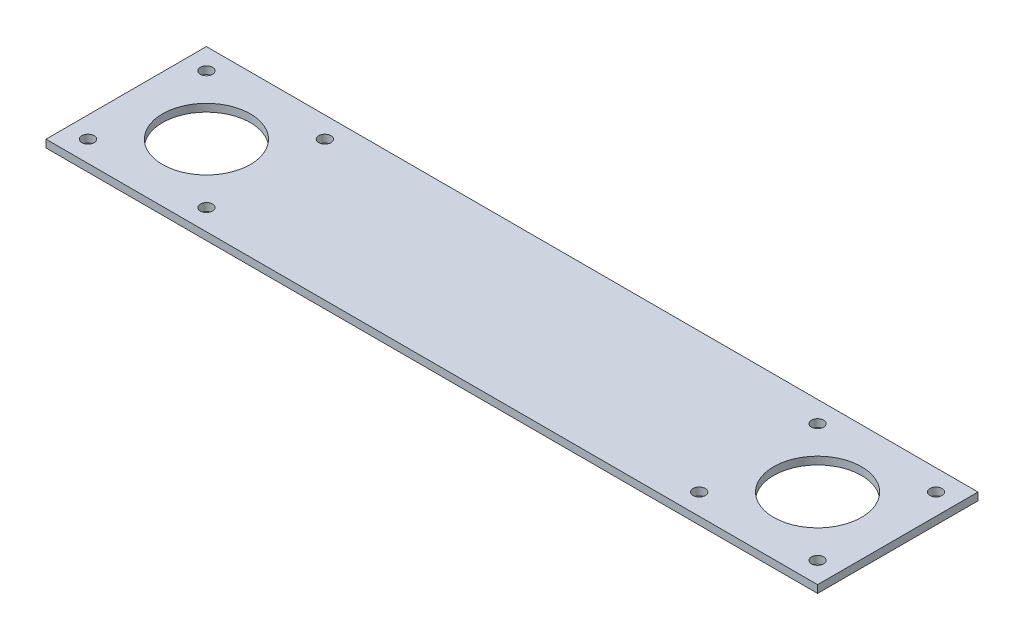
SolidWorks part; units mm, degrees
ref_plane "Front Plane" through (0, 0, 0) normal (0, 0, 1) x (1, 0, 0)
ref_plane "Top Plane" through (0, 0, 0) normal (0, 1, 0) x (1, 0, 0)
ref_plane "Right Plane" through (0, 0, 0) normal (1, 0, 0) x (0, 0, -1)
sketch "Sketch1" plane through (0, 0, 0) normal (0, 1, 0) x (1, 0, 0)
  line L0 (0, -55) -> (0, 55) construction
  line L1 (-140, -21) -> (140, -21)
  line L2 (-140, -21) -> (-140, 21)
  line L3 (-140, 21) -> (140, 21)
  line L4 (140, -21) -> (140, 21)
  line L5 (-140, -21) -> (140, 21) construction
  line L6 (-140, 21) -> (140, -21) construction
  line L7 (-101, 21) -> (-59, 21) construction
  line L8 (-101, 21) -> (-101, -21)
  line L9 (-101, -21) -> (-59, -21) construction
  line L10 (-59, 21) -> (-59, -21) construction
  line L11 (-101, 21) -> (-59, -21) construction
  line L12 (-101, -21) -> (-59, 21) construction
  line L13 (101, -21) -> (59, 21) construction
  line L14 (101, 21) -> (59, -21) construction
  line L15 (59, 21) -> (59, -21) construction
  line L16 (101, -21) -> (59, -21) construction
  line L17 (101, 21) -> (101, -21)
  line L18 (101, 21) -> (59, 21) construction
  line L19 (-17.5, 0) -> (17.5, 0) construction
  circle A0 centre (-80, 0) radius 62.5 construction
  circle A1 centre (-64.5, 15.5) radius 1.6
  circle A2 centre (-64.5, -15.5) radius 1.6
  circle A3 centre (-95.5, -15.5) radius 1.6
  circle A4 centre (-95.5, 15.5) radius 1.6
  circle A5 centre (80, 0) radius 62.5 construction
  circle A6 centre (95.5, 15.5) radius 1.6
  circle A7 centre (95.5, -15.5) radius 1.6
  circle A8 centre (64.5, -15.5) radius 1.6
  circle A9 centre (64.5, 15.5) radius 1.6
  circle A10 centre (0, 0) radius 25 construction
  circle A11 centre (-80, 0) radius 11.5
  circle A12 centre (80, 0) radius 11.5
  point P0 (0, 0)
  point P23 (-80, 0)
  point P43 (80, 0)
  dimension "D3" = 125
  dimension "D5" = 3.2
  dimension "D8" = 160
  dimension "D10" = 50
  dimension "D11" = 23
  dimension "D1" = 42
  dimension "D2" = 280
  dimension "D4" = 42
  dimension "D7" = 31
  dimension "D9" = 35
  dimension "D6" = 4
extrude "Boss-Extrude1" add sketch "Sketch1" along normal blind 2 contours L17 L3 L8 L1 A8 A6 A4 A3 A2 A1 A7 A9 region at (0, 0, 0)
